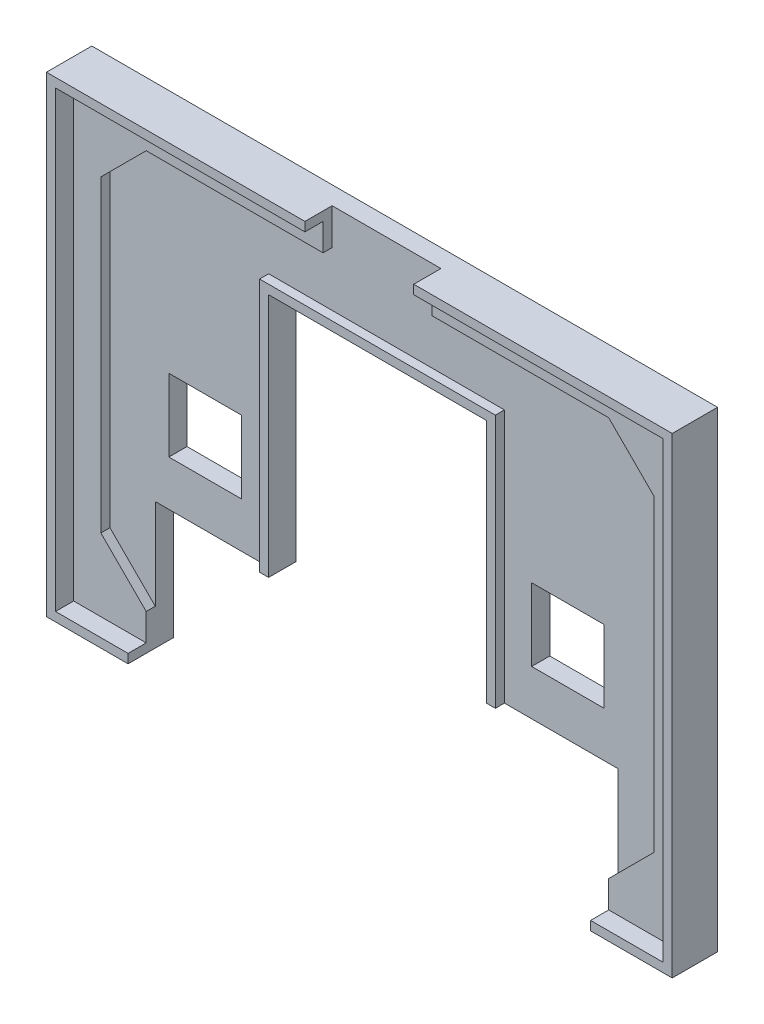
SolidWorks part; units mm, degrees
ref_plane "Přední rovina" through (0, 0, 0) normal (0, 0, 1) x (1, 0, 0)
ref_plane "Horní rovina" through (0, 0, 0) normal (0, 1, 0) x (1, 0, 0)
ref_plane "Pravá rovina" through (0, 0, 0) normal (1, 0, 0) x (0, 0, -1)
sketch "Skica1" plane through (0, 0, 0) normal (0, 0, 1) x (1, 0, 0)
  line L1 (-33.5, -25) -> (33.5, -25)
  line L2 (-33.5, -25) -> (-33.5, 25)
  line L3 (-33.5, 25) -> (33.5, 25)
  line L4 (33.5, -25) -> (33.5, 25)
  line L5 (-33.5, -25) -> (33.5, 25) construction
  line L6 (-33.5, 25) -> (33.5, -25) construction
  point P0 (0, 0)
  dimension "D1" = 67
  dimension "D2" = 50
extrude "Přidat vysunutím1" add sketch "Skica1" along normal blind 3
sketch "Skica2" plane through (0, 0, 3) normal (0, 0, 1) x (1, 0, 0)
  line L0 (-1000, 0) -> (49000, 0) construction
  line L1 (0, -1000) -> (0, 49000) construction
  line L2 (-1000, -22) -> (49000, -22) construction
  line L3 (-25.5, -1000) -> (-25.5, 49000) construction
  line L4 (-30.5, -1000) -> (-30.5, 49000) construction
  line L6 (-33.5, -25) -> (33.5, -25) construction
  line L7 (-25.5, -22) -> (-30.5, -17)
  line L8 (-30.5, -17) -> (-30.5, 17)
  line L9 (-25.5, -22) -> (25.5, -22)
  line L10 (30.5, -17) -> (30.5, 17)
  line L11 (25.5, -22) -> (30.5, -17)
  line L12 (25.5, 22) -> (30.5, 17)
  line L13 (-25.5, 22) -> (25.5, 22)
  line L14 (-25.5, 22) -> (-30.5, 17)
  point P20 (0, -22)
  point P21 (30.5, 0)
  point P24 (-30.5, 0)
  dimension "D1" = 30.5
  dimension "D2" = 5
  dimension "D3" = 3
  dimension "D4" = 45
extrude "Odebrat vysunutím1" cut sketch "Skica2" against normal offset from surface (1 mm away) 2 up to face at (0, 0, 0)
sketch "Skica3" plane through (0, 0, 0) normal (0, 0, -1) x (-1, 0, 0)
  line L0 (0, -1000) -> (0, 49000) construction
  line L1 (33.5, -25) -> (-33.5, -25) construction
  line L2 (24, 1) -> (16, 1)
  line L3 (24, 1) -> (24, -7)
  line L4 (24, -7) -> (16, -7)
  line L5 (16, 1) -> (16, -7)
  line L6 (-16, 1) -> (-16, -7)
  line L7 (33.5, -25) -> (-33.5, -25) construction
  line L8 (25.5, -25) -> (-25.5, -25)
  line L9 (25.5, -25) -> (25.5, -12)
  line L11 (-25.5, -25) -> (-25.5, -12)
  line L12 (-24, -7) -> (-16, -7)
  line L13 (25.5, -12) -> (12, -12)
  line L15 (12, -12) -> (12, 15)
  line L16 (12, 15) -> (-12, 15)
  line L17 (-12, -12) -> (-12, 15)
  line L18 (-12, -12) -> (-25.5, -12)
  line L19 (-24, 1) -> (-24, -7)
  line L20 (-24, 1) -> (-16, 1)
  dimension "D1" = 16
  dimension "D2" = 8
  dimension "D3" = 18
  dimension "D4" = 13
  dimension "D5" = 51
  dimension "D6" = 24
  dimension "D7" = 27
extrude "Odebrat vysunutím2" cut sketch "Skica3" against normal through all
sketch "Skica4" plane through (0, 0, 2) normal (0, 0, 1) x (1, 0, 0)
  line L0 (12, 15) -> (12, -12) construction
  line L1 (-12, -12) -> (-12, 15) construction
  line L2 (-12, 15) -> (12, 15) construction
  line L3 (12, 15) -> (12, -12)
  line L4 (-12, -12) -> (-12, 15)
  line L5 (-12, 15) -> (12, 15)
extrude "Vysunout tenkostěnný1" add sketch "Skica4" along normal up to surface (1 mm away) thin up to face at (0, -3.5714, 3) thin type one direction reverse wall 1
sketch "Skica5" plane through (0, 0, 0) normal (0, 0, -1) x (-1, 0, 0)
  line L0 (-33.5, 25) -> (33.5, 25) construction
  line L1 (33.5, 25) -> (33.5, -25) construction
  line L2 (33.5, -25) -> (25.5, -25) construction
  line L3 (-33.5, -25) -> (-33.5, 25) construction
  line L4 (-25.5, -25) -> (-33.5, -25) construction
  line L5 (-33.5, 25) -> (33.5, 25)
  line L6 (33.5, 25) -> (33.5, -25)
  line L7 (33.5, -25) -> (25.5, -25)
  line L8 (-33.5, -25) -> (-33.5, 25)
  line L9 (-25.5, -25) -> (-33.5, -25)
extrude "Vysunout tenkostěnný2" add sketch "Skica5" against normal blind 5 thin thin type one direction reverse wall 1
sketch "Skica6" plane through (0, 0, 2) normal (0, 0, 1) x (1, 0, 0)
  line L0 (0, -1000) -> (0, 49000) construction
  line L1 (25.5, 22) -> (-25.5, 22) construction
  line L2 (-6, 22) -> (6, 22)
  line L3 (-6, 22) -> (-6, 26)
  line L4 (-6, 26) -> (6, 26)
  line L5 (6, 22) -> (6, 26)
  line L6 (34.5, 26) -> (-34.5, 26) construction
  dimension "D1" = 12
extrude "Odebrat vysunutím3" cut sketch "Skica6" along normal through all
sketch "Skica7" plane through (0, 0, 0) normal (0, 0, -1) x (-1, 0, 0)
  line L0 (0, 0) -> (0, 39.8227) construction
  line L1 (-19.0673, 21.7997) -> (-19.0673, 19.8467)
  line L24 (-19.0673, 19.8467) -> (-17.2673, 19.8467)
  line L25 (-17.2673, 19.8467) -> (-17.2673, 17.9467)
  line L26 (-17.2673, 17.9467) -> (-15.4673, 17.9467)
  line L27 (-15.4673, 17.9467) -> (-15.4673, 11.8368)
  line L28 (-15.4673, 11.8368) -> (-17.2673, 11.8368)
  line L29 (-17.2673, 11.8368) -> (-17.2673, 10.0637)
  line L30 (-17.2673, 10.0637) -> (-15.4673, 10.0637)
  line L31 (-15.4673, 10.0637) -> (-15.4673, 8.2637)
  line L32 (-15.4673, 8.2637) -> (-17.2673, 8.2637)
  line L33 (-17.2673, 8.2637) -> (-17.2673, 6.4637)
  line L34 (-17.2673, 6.4637) -> (-19.0873, 6.4637)
  line L35 (-19.0873, 6.4637) -> (-19.0873, 8.2737)
  line L36 (-19.0873, 8.2737) -> (-17.2773, 8.2737)
  line L37 (-17.2773, 8.2737) -> (-17.2773, 10.0537)
  line L38 (-17.2773, 10.0537) -> (-19.0773, 10.0537)
  line L39 (-19.0773, 10.0537) -> (-19.0773, 11.8368)
  line L40 (-19.0773, 11.8368) -> (-20.9273, 11.8368)
  line L41 (-20.9273, 11.8368) -> (-20.9273, 10.0537)
  line L42 (-20.9273, 10.0537) -> (-25.4842, 10.0537)
  line L44 (-27.3442, 21.7997) -> (-19.0673, 21.7997)
  line L45 (27.3442, 21.7997) -> (19.0673, 21.7997)
  line L46 (-25.4842, 11.8368) -> (-25.4842, 10.0537)
  line L47 (-27.3342, 11.8368) -> (-25.4842, 11.8368)
  line L48 (-27.3342, 10.0537) -> (-27.3342, 11.8368)
  line L49 (-29.1342, 10.0537) -> (-27.3342, 10.0537)
  line L50 (-29.1342, 8.2737) -> (-29.1342, 10.0537)
  line L51 (-27.3242, 8.2737) -> (-29.1342, 8.2737)
  line L52 (-27.3242, 6.4637) -> (-27.3242, 8.2737)
  line L53 (-29.1442, 6.4637) -> (-27.3242, 6.4637)
  line L54 (-29.1442, 8.2637) -> (-29.1442, 6.4637)
  line L55 (-30.9442, 8.2637) -> (-29.1442, 8.2637)
  line L56 (-30.9442, 10.0637) -> (-30.9442, 8.2637)
  line L57 (-29.1442, 10.0637) -> (-30.9442, 10.0637)
  line L58 (-29.1442, 11.8368) -> (-29.1442, 10.0637)
  line L59 (-30.9442, 11.8368) -> (-29.1442, 11.8368)
  line L60 (-30.9442, 17.9467) -> (-30.9442, 11.8368)
  line L61 (-29.1442, 17.9467) -> (-30.9442, 17.9467)
  line L62 (-29.1442, 19.8467) -> (-29.1442, 17.9467)
  line L63 (-27.3442, 19.8467) -> (-29.1442, 19.8467)
  line L64 (-27.3442, 21.7997) -> (-27.3442, 19.8467)
  line L65 (27.3442, 21.7997) -> (27.3442, 19.8467)
  line L66 (27.3442, 19.8467) -> (29.1442, 19.8467)
  line L67 (29.1442, 19.8467) -> (29.1442, 17.9467)
  line L68 (29.1442, 17.9467) -> (30.9442, 17.9467)
  line L69 (30.9442, 17.9467) -> (30.9442, 11.8368)
  line L70 (30.9442, 11.8368) -> (29.1442, 11.8368)
  line L71 (29.1442, 11.8368) -> (29.1442, 10.0637)
  line L72 (29.1442, 10.0637) -> (30.9442, 10.0637)
  line L73 (30.9442, 10.0637) -> (30.9442, 8.2637)
  line L74 (30.9442, 8.2637) -> (29.1442, 8.2637)
  line L75 (29.1442, 8.2637) -> (29.1442, 6.4637)
  line L76 (29.1442, 6.4637) -> (27.3242, 6.4637)
  line L77 (27.3242, 6.4637) -> (27.3242, 8.2737)
  line L78 (27.3242, 8.2737) -> (29.1342, 8.2737)
  line L79 (29.1342, 8.2737) -> (29.1342, 10.0537)
  line L80 (29.1342, 10.0537) -> (27.3342, 10.0537)
  line L81 (27.3342, 10.0537) -> (27.3342, 11.8368)
  line L82 (27.3342, 11.8368) -> (25.4842, 11.8368)
  line L83 (25.4842, 11.8368) -> (25.4842, 10.0537)
  line L84 (20.9273, 10.0537) -> (25.4842, 10.0537)
  line L85 (20.9273, 11.8368) -> (20.9273, 10.0537)
  line L86 (19.0773, 11.8368) -> (20.9273, 11.8368)
  line L87 (19.0773, 10.0537) -> (19.0773, 11.8368)
  line L88 (17.2773, 10.0537) -> (19.0773, 10.0537)
  line L89 (17.2773, 8.2737) -> (17.2773, 10.0537)
  line L90 (19.0873, 8.2737) -> (17.2773, 8.2737)
  line L91 (19.0873, 6.4637) -> (19.0873, 8.2737)
  line L92 (17.2673, 6.4637) -> (19.0873, 6.4637)
  line L93 (17.2673, 8.2637) -> (17.2673, 6.4637)
  line L94 (15.4673, 8.2637) -> (17.2673, 8.2637)
  line L95 (15.4673, 10.0637) -> (15.4673, 8.2637)
  line L96 (17.2673, 10.0637) -> (15.4673, 10.0637)
  line L97 (17.2673, 11.8368) -> (17.2673, 10.0637)
  line L98 (15.4673, 11.8368) -> (17.2673, 11.8368)
  line L99 (15.4673, 17.9467) -> (15.4673, 11.8368)
  line L100 (17.2673, 17.9467) -> (15.4673, 17.9467)
  line L101 (17.2673, 19.8467) -> (17.2673, 17.9467)
  line L102 (19.0673, 19.8467) -> (17.2673, 19.8467)
  line L103 (19.0673, 21.7997) -> (19.0673, 19.8467)
extrude "Odebrat vysunutím4" cut sketch "Skica7" against normal blind 1
sketch "Skica8" plane through (0, 0, 1) normal (0, 0, -1) x (-1, 0, 0)
  line L1 (-29.1442, 16.1467) -> (-25.5442, 16.1467)
  line L2 (-29.1442, 16.1467) -> (-29.1442, 14.3371)
  line L3 (-29.1442, 14.3371) -> (-25.5442, 14.3371)
  line L4 (-25.5442, 16.1467) -> (-25.5442, 14.3371)
  line L5 (-29.1442, 17.9467) -> (-30.9442, 17.9467) construction
  line L8 (-30.9442, 17.9467) -> (-30.9442, 11.8368) construction
  line L9 (-23.2058, 10.0537) -> (-23.2058, 24.0477) construction
  line L10 (-25.4842, 10.0537) -> (-20.9273, 10.0537) construction
  line L11 (-17.2673, 14.3371) -> (-20.8673, 14.3371)
  line L12 (-20.8673, 16.1467) -> (-20.8673, 14.3371)
  line L13 (-17.2673, 16.1467) -> (-20.8673, 16.1467)
  line L14 (-17.2673, 16.1467) -> (-17.2673, 14.3371)
  line L16 (0, 0) -> (0, 31.7096) construction
  line L17 (29.1442, 14.3371) -> (25.5442, 14.3371)
  line L18 (25.5442, 16.1467) -> (25.5442, 14.3371)
  line L19 (29.1442, 16.1467) -> (25.5442, 16.1467)
  line L20 (29.1442, 16.1467) -> (29.1442, 14.3371)
  line L21 (17.2673, 16.1467) -> (17.2673, 14.3371)
  line L22 (17.2673, 16.1467) -> (20.8673, 16.1467)
  line L23 (20.8673, 16.1467) -> (20.8673, 14.3371)
  line L24 (17.2673, 14.3371) -> (20.8673, 14.3371)
  dimension "D1" = 1.8
  dimension "D2" = 1.8096
  dimension "D3" = 1.8
  dimension "D4" = 3.6
extrude "Přidat vysunutím2" add sketch "Skica8" along normal blind 1
sketch "Skica9" plane through (0, 0, 0) normal (0, 0, -1) x (-1, 0, 0)
  line L0 (30.9442, 8.2637) -> (30.9442, 10.0637) construction
  line L1 (-19.0873, 6.4637) -> (-17.2673, 6.4637) construction
  text T0 "ZARK" font "BLOXAT" height 5.8
  dimension "D1" = 41.8948
  dimension "D2" = 11.0584
extrude "Odebrat vysunutím5" cut sketch "Skica9" against normal blind 1
